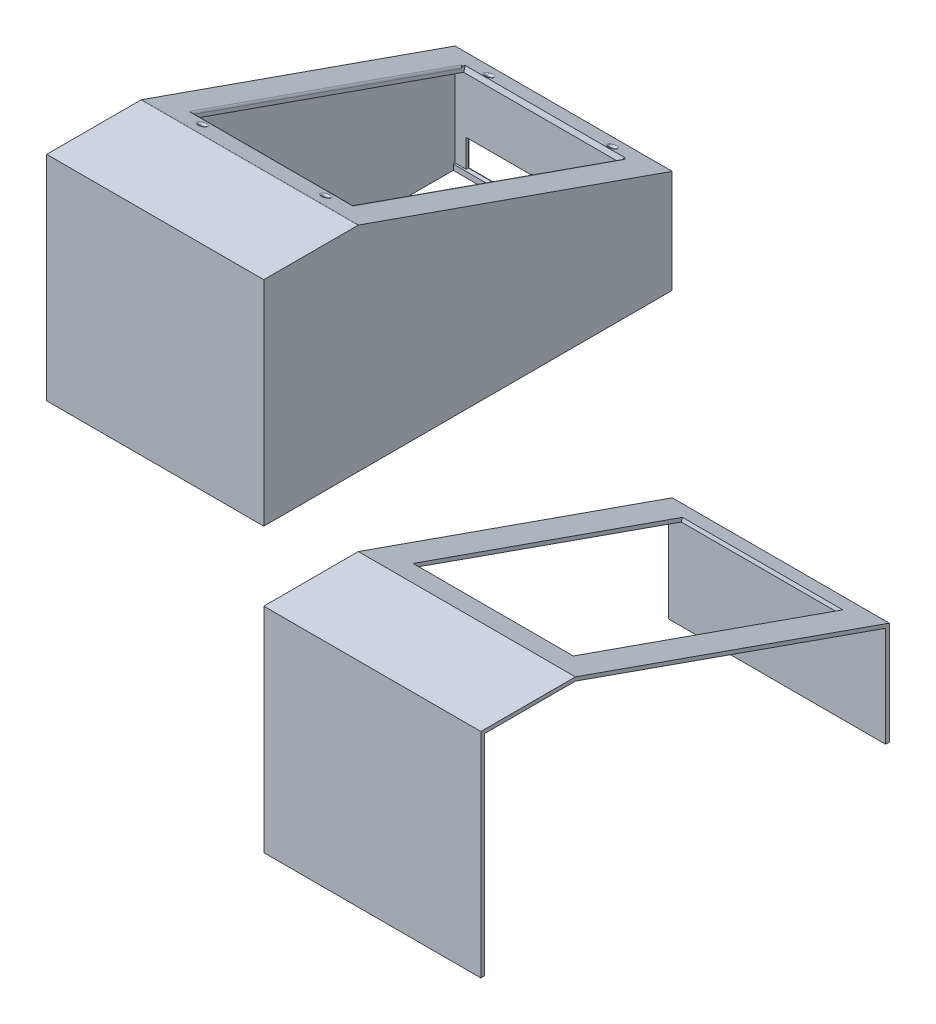
SolidWorks part; units mm, degrees
ref_plane "Alzado" through (0, 0, 0) normal (0, 0, 1) x (1, 0, 0)
ref_plane "Planta" through (0, 0, 0) normal (0, 1, 0) x (1, 0, 0)
ref_plane "Vista lateral" through (0, 0, 0) normal (1, 0, 0) x (0, 0, -1)
sketch "Sketch1" plane through (0, 0, 0) normal (1, 0, 0) x (0, 0, -1)
  line L3 (157.3381, -22.7425) -> (157.3381, 37.2575) construction
  line L4 (157.3381, 37.2575) -> (50.3381, 74.8888)
  line L7 (50.3381, 74.8888) -> (-13.2647, 97.2575)
  line L8 (-13.2647, 97.2575) -> (-64.6619, 97.2575)
  line L9 (-64.6619, 97.2575) -> (-64.6619, 95.2575)
  line L10 (-64.6619, 95.2575) -> (-13.2647, 95.2575)
  line L11 (-13.2647, 95.2575) -> (157.3381, 35.2575)
  line L12 (157.3381, 35.2575) -> (157.3381, -22.7425)
  line L13 (157.3381, -22.7425) -> (159.3381, -22.7425)
  line L14 (157.3381, 37.2575) -> (159.3381, 36.5258)
  line L15 (159.3381, 36.5258) -> (159.3381, -22.7425)
extrude "Boss-Extrude1" add sketch "Sketch1" along normal blind 118
sketch "Sketch2" plane through (0, 0, -159.3381) normal (0, 0, -1) x (-1, 0, 0)
  line L0 (0, -22.7425) -> (-8, -22.7425) construction
  line L1 (-118, -22.7425) -> (0, -22.7425) construction
  line L3 (-8, -22.7425) -> (-52, -22.7425)
  line L4 (-8, -22.7425) -> (-8, -0.7425)
  line L5 (-8, -0.7425) -> (-52, -0.7425)
  line L6 (-52, -22.7425) -> (-52, -0.7425)
  dimension "D1" = 8
  dimension "D2" = 22
  dimension "D3" = 44
extrude "Cut-Extrude1" cut sketch "Sketch2" against normal blind 118
sketch "Sketch3" plane through (0, 95.2575, 0) normal (0, -1, 0) x (1, 0, 0)
  line L0 (118, 64.6619) -> (118, 13.2647) construction
  line L1 (0, 64.6619) -> (118, 64.6619)
  line L2 (0, 64.6619) -> (0, 62.6619)
  line L3 (0, 62.6619) -> (118, 62.6619)
  line L4 (118, 64.6619) -> (118, 62.6619)
  dimension "D1" = 2
sketch "Sketch48" plane through (0, 0, -159.3381) normal (0, 0, -1) x (-1, 0, 0)
  line L0 (-8, -22.7425) -> (-8, -0.7425) construction
  line L1 (-52, -0.7425) -> (-8, -0.7425)
  line L2 (-52, -0.7425) -> (-52, -2.7425)
  line L3 (-52, -2.7425) -> (-8, -2.7425)
  line L4 (-8, -0.7425) -> (-8, -2.7425)
  dimension "D1" = 2
extrude "Boss-Extrude28" add sketch "Sketch48" against normal up to vertex
sketch "Sketch49" plane through (0, 0, -159.3381) normal (0, 0, -1) x (-1, 0, 0)
  line L0 (-8, -22.7425) -> (-8, -2.7425) construction
  line L1 (-52, -2.7425) -> (-8, -2.7425)
  line L2 (-52, -2.7425) -> (-52, -5.2425)
  line L3 (-52, -5.2425) -> (-8, -5.2425)
  line L4 (-8, -2.7425) -> (-8, -5.2425)
  dimension "D1" = 2.5
extrude "Boss-Extrude29" add sketch "Sketch49" against normal up to vertex
sketch "Sketch50" plane through (0, 0, -159.3381) normal (0, 0, -1) x (-1, 0, 0)
  line L0 (-52, -5.2425) -> (-8, -5.2425) construction
  line L1 (-8, -5.2425) -> (-9.5, -5.2425)
  line L2 (-8, -5.2425) -> (-8, -22.7425)
  line L3 (-8, -22.7425) -> (-9.5, -22.7425)
  line L4 (-9.5, -5.2425) -> (-9.5, -22.7425)
  line L5 (-52, -22.7425) -> (-48.5, -22.7425)
  line L6 (-52, -22.7425) -> (-52, -5.2425)
  line L7 (-52, -5.2425) -> (-48.5, -5.2425)
  line L8 (-48.5, -22.7425) -> (-48.5, -5.2425)
  dimension "D1" = 3.5
  dimension "D2" = 1.5
extrude "Boss-Extrude30" add sketch "Sketch50" against normal up to vertex
sketch "Sketch51" plane through (0, 0, -159.3381) normal (0, 0, -1) x (-1, 0, 0)
  line L0 (0, -22.7425) -> (0, 36.5258) construction
  line L1 (-118, -22.7425) -> (0, -22.7425)
  line L2 (-118, -22.7425) -> (-118, -19.2425)
  line L3 (-118, -19.2425) -> (0, -19.2425)
  line L4 (0, -22.7425) -> (0, -19.2425)
  dimension "D1" = 3.5
extrude "Boss-Extrude31" add sketch "Sketch51" against normal up to vertex
sketch "Sketch52" plane through (0, 82.4004, -28.9797) normal (0, 0.9434, -0.3318) x (1, 0, 0)
  line L0 (118, 136.0652) -> (118, -44.7809) construction
  line L1 (15.45, 123.5652) -> (102.55, 123.5652)
  line L2 (15.45, 123.5652) -> (15.45, -31.6348)
  line L3 (15.45, -31.6348) -> (102.55, -31.6348)
  line L4 (102.55, 123.5652) -> (102.55, -31.6348)
  line L6 (118, 136.0652) -> (0, 136.0652) construction
  dimension "D1" = 87.1
  dimension "D2" = 155.2
  dimension "D3" = 15.45
  dimension "D4" = 12.5
extrude "Cut-Extrude11" cut sketch "Sketch52" against normal blind 2
sketch "Sketch53" plane through (0, 0, 0) normal (-1, 0, 0) x (0, 0, 1)
  line L0 (-151.3116, 39.377) -> (-159.3381, 36.5541)
  line L1 (-157.3381, 37.2575) -> (13.2647, 97.2575) construction
  line L2 (-159.3381, 36.5541) -> (-159.3381, 36.3733)
  line L3 (-159.3381, -22.7425) -> (-159.3381, 36.5258) construction
  line L4 (-159.3381, 36.3733) -> (-153.7496, 38.3387)
  line L5 (-153.7496, 38.3387) -> (-151.3116, 39.377)
extrude "Boss-Extrude32" add sketch "Sketch53" against normal up to vertex (118 mm away)
sketch "Sketch54" plane through (0, 80.6205, -28.3538) normal (0, -0.9434, 0.3318) x (1, 0, 0)
  line L0 (15.45, 31.6348) -> (102.55, 31.6348) construction
  line L1 (10.45, -133.5652) -> (107.55, -133.5652)
  line L2 (10.45, -133.5652) -> (10.45, 41.6348)
  line L3 (10.45, 41.6348) -> (107.55, 41.6348)
  line L4 (107.55, -133.5652) -> (107.55, 41.6348)
  line L5 (10.45, -133.5652) -> (107.55, 41.6348) construction
  line L6 (10.45, 41.6348) -> (107.55, -133.5652) construction
  line L7 (15.45, -123.5652) -> (15.45, 31.6348) construction
  line L8 (102.55, 31.6348) -> (102.55, -123.5652) construction
  line L9 (102.55, -123.5652) -> (15.45, -123.5652) construction
  point P0 (59, -45.9652)
  dimension "D1" = 10
  dimension "D2" = 5
  dimension "D3" = 5
  dimension "D4" = 10
extrude "Boss-Extrude33" add sketch "Sketch54" along normal blind 1
sketch "Sketch55" plane through (0, 80.6205, -28.3538) normal (0, 0.9434, -0.3318) x (1, 0, 0)
  line L1 (15.45, 123.5652) -> (102.55, 123.5652)
  line L2 (15.45, 123.5652) -> (15.45, -31.6348)
  line L3 (15.45, -31.6348) -> (102.55, -31.6348)
  line L4 (102.55, 123.5652) -> (102.55, -31.6348)
extrude "Cut-Extrude12" cut sketch "Sketch55" against normal blind 1
sketch "Sketch56" plane through (0, 79.6772, -28.022) normal (0, -0.9434, 0.3318) x (1, 0, 0)
  line L0 (10.45, 41.6348) -> (10.45, -133.5652) construction
  line L1 (15.45, 31.6348) -> (102.55, 31.6348) construction
  line L2 (107.55, -133.5652) -> (107.55, 41.6348) construction
  line L3 (102.55, -123.5652) -> (15.45, -123.5652) construction
  circle A0 centre (92.55, 36.6348) radius 2.5059
  circle A1 centre (25.45, 36.6348) radius 1.5
  circle A2 centre (25.45, -128.5652) radius 1.5
  circle A3 centre (92.55, -128.5652) radius 1.5
  dimension "D1" = 3
  dimension "D7" = 3
  dimension "D9" = 3
  dimension "D2" = 15
  dimension "D3" = 5
  dimension "D4" = 5
  dimension "D5" = 15
  dimension "D6" = 15
  dimension "D8" = 5
  dimension "D10" = 5
  dimension "D11" = 15
extrude "Cut-Extrude13" cut sketch "Sketch56" against normal through all
sketch "Sketch57" plane through (0, 79.6772, -28.022) normal (0, -0.9434, 0.3318) x (1, 0, 0)
  circle A0 centre (92.55, 36.6348) radius 2.5059
extrude "Boss-Extrude35" add sketch "Sketch57" against normal up to vertex (2.8867 mm away)
sketch "Sketch58" plane through (0, 79.6772, -28.022) normal (0, -0.9434, 0.3318) x (1, 0, 0)
  line L0 (15.45, 31.6348) -> (102.55, 31.6348) construction
  line L1 (107.55, -133.5652) -> (107.55, 41.6348) construction
  circle A0 centre (92.55, 36.6348) radius 1.5
  dimension "D1" = 5
  dimension "D2" = 15
extrude "Cut-Extrude14" cut sketch "Sketch58" against normal through all
extrude "Boss-Extrude2" add sketch "Sketch3" along normal blind 114.04
sketch "Sketch5" plane through (0, 0, 64.6619) normal (0, 0, 1) x (1, 0, 0)
  line L7 (118, -18.7825) -> (0, -18.7825) construction
  line L8 (108, -18.7825) -> (69, -18.7825)
  line L9 (108, -18.7825) -> (108, -8.7825)
  line L10 (108, -8.7825) -> (69, -8.7825)
  line L11 (69, -18.7825) -> (69, -8.7825)
  line L12 (59, -18.7825) -> (59, -8.6532) construction
  line L13 (118, 97.2575) -> (118, -18.7825) construction
  dimension "D1" = 10
  dimension "D2" = 10
  dimension "D3" = 10
extrude "Boss-Extrude3" add sketch "Sketch5" against normal blind 10
sketch "Sketch6" plane through (0, 0, 62.6619) normal (0, 0, -1) x (-1, 0, 0)
  line L0 (0, -18.7825) -> (0, 95.2575) construction
  line L1 (-118, -18.7825) -> (0, -18.7825)
  line L2 (-118, -18.7825) -> (-118, -16.7825)
  line L3 (-118, -16.7825) -> (0, -16.7825)
  line L4 (0, -18.7825) -> (0, -16.7825)
  dimension "D1" = 2
extrude "Boss-Extrude4" add sketch "Sketch6" along normal blind 1
sketch "Sketch7" plane through (0, 0, 64.6619) normal (0, 0, 1) x (1, 0, 0)
  line L1 (0, -18.7825) -> (118, -18.7825)
  line L2 (0, -18.7825) -> (0, -22.7425)
  line L3 (0, -22.7425) -> (118, -22.7425)
  line L4 (118, -18.7825) -> (118, -22.7425)
extrude "Cut-Extrude2" cut sketch "Sketch7" against normal through all
sketch "Sketch8" plane through (0, 0, -159.3381) normal (0, 0, -1) x (-1, 0, 0)
  line L0 (0, -18.7825) -> (0, 36.5541) construction
  line L1 (-118, -18.7825) -> (0, -18.7825)
  line L2 (-118, -18.7825) -> (-118, -15.7825)
  line L3 (-118, -15.7825) -> (0, -15.7825)
  line L4 (0, -18.7825) -> (0, -15.7825)
  dimension "D1" = 3
extrude "Boss-Extrude5" add sketch "Sketch8" against normal up to vertex
sketch "Sketch9" plane through (0, 0, 0) normal (-1, 0, 0) x (0, 0, 1)
  line L0 (13.2647, 95.2575) -> (-157.3381, 35.2575) construction
  line L1 (-157.3381, -18.7825) -> (-155.3381, -18.7825)
  line L2 (-157.3381, -18.7825) -> (-157.3381, 35.9609)
  line L3 (-157.3381, 35.9609) -> (-155.3381, 35.9609)
  line L4 (-155.3381, -18.7825) -> (-155.3381, 35.9609)
  dimension "D1" = 2
extrude "Boss-Extrude6" add sketch "Sketch9" against normal up to vertex (118 mm away)
sketch "Sketch12" plane through (0, 0, -157.3381) normal (0, 0, -1) x (-1, 0, 0)
  line L1 (-52, -15.7825) -> (-8, -15.7825)
  line L2 (-52, -15.7825) -> (-52, -0.7425)
  line L3 (-52, -0.7425) -> (-8, -0.7425)
  line L4 (-8, -15.7825) -> (-8, -0.7425)
extrude "Cut-Extrude4" cut sketch "Sketch12" against normal blind 116
sketch "Sketch13" plane through (0, 0, 0) normal (-1, 0, 0) x (0, 0, 1)
  line L1 (-159.3381, -18.7825) -> (-157.3381, -18.7825)
  line L2 (-159.3381, -18.7825) -> (-159.3381, 42.3145)
  line L3 (-159.3381, 42.3145) -> (-157.3381, 42.3145)
  line L4 (-157.3381, -18.7825) -> (-157.3381, 42.3145)
  dimension "D1" = 2
sketch3d "3DSketch1"
  point P0 (82.8961, 95.2575, 47.2846)
sketch "Sketch59" plane through (0, 0, -159.3381) normal (0, 0, -1) x (-1, 0, 0)
  line L1 (-48.5, -5.2425) -> (-43.5, -5.2425)
  line L2 (-48.5, -5.2425) -> (-48.5, -0.2425)
  line L3 (-48.5, -0.2425) -> (-43.5, -0.2425)
  line L4 (-43.5, -5.2425) -> (-43.5, -0.2425)
  dimension "D1" = 5
  dimension "D2" = 5
extrude "Cut-Extrude15" cut sketch "Sketch59" against normal blind 10
extrude "Cut-Extrude5" cut sketch "Sketch13" against normal through all
sketch "Sketch15" plane through (0, 0, -155.3381) normal (0, 0, 1) x (1, 0, 0)
  line L0 (118, -18.7825) -> (118, 35.9609) construction
  line L1 (0, -18.7825) -> (118, -18.7825)
  line L2 (0, -18.7825) -> (0, -15.7825)
  line L3 (0, -15.7825) -> (118, -15.7825)
  line L4 (118, -18.7825) -> (118, -15.7825)
  dimension "D1" = 3
extrude "Boss-Extrude7" add sketch "Sketch15" along normal blind 1
sketch "Sketch26" plane through (118, 0, 0) normal (1, 0, 0) x (0, 0, -1)
  line L0 (-64.6619, -18.7825) -> (-64.6619, 97.2575)
  line L1 (-64.6619, 97.2575) -> (-13.2647, 97.2575)
  line L2 (-13.2647, 97.2575) -> (157.3381, 37.2575)
  line L3 (157.3381, 37.2575) -> (157.3381, -18.7825)
  line L4 (157.3381, -18.7825) -> (-64.6619, -18.7825)
extrude "Boss-Extrude13" add sketch "Sketch26" against normal blind 2
sketch "Sketch28" plane through (0, 0, 0) normal (-1, 0, 0) x (0, 0, 1)
  line L0 (64.6619, -18.7825) -> (64.6619, 97.2575)
  line L1 (64.6619, 97.2575) -> (13.2647, 97.2575)
  line L2 (13.2647, 97.2575) -> (-157.3381, 37.2575)
  line L3 (-157.3381, 37.2575) -> (-157.3381, -18.7825)
  line L4 (-157.3381, -18.7825) -> (64.6619, -18.7825)
extrude "Boss-Extrude16" add sketch "Sketch28" against normal blind 2
fillet "Fillet9" radius 1 31 edges at (30, -15.7825, -157.3381) (59, -18.7825, -157.3381) (50.25, -0.7425, -157.3381) (46, -0.2425, -157.3381) (25.75, -0.7425, -157.3381) (0, 9.2375, -157.3381) (118, 9.2375, -157.3381) (118, -18.7825, -46.3381) (0, 39.2375, 64.6619) (118, 39.2375, 64.6619) (59, -18.7825, 64.6619) (59, 97.2575, 64.6619) (0, 97.2575, 38.9633) (118, 97.2575, 38.9633) (59, 37.2575, -157.3381) (0, 67.2575, -72.0367) (118, 67.2575, -72.0367) (59, 97.2575, 13.2647) (0, -18.7825, -46.3381) (8, -8.2625, -157.3381) (52, -8.2625, -157.3381) (92.55, 94.0572, 4.165) (92.55, 39.2482, -151.6779) (25.45, 39.2482, -151.6779) (25.45, 94.0572, 4.165) (102.55, 67.1503, -72.3414) (59, 41.4047, -145.5461) (15.45, 67.1503, -72.3414) (59, 92.896, 0.8632) (43.5, -0.4925, -157.3381) (48.5, -0.4925, -157.3381)
fillet "Fillet10" radius 1 13 edges at (59, 95.2575, 13.2647) (116, 65.6092, -71.0367) (59, 35.9609, -155.3381) (2, 65.6092, -71.0367) (116, 95.2575, 37.9633) (116, 39.2375, 62.6619) (2, 39.2375, 62.6619) (59, 95.2575, 62.6619) (2, 95.2575, 37.9633) (59, 94.4339, 10.9228) (10.45, 65.3705, -71.7155) (59, 36.3071, -154.3537) (107.55, 65.3705, -71.7155)
sketch "Sketch30" plane through (0, 82.4004, -28.9797) normal (0, 0.9434, -0.3318) x (1, 0, 0)
  line L1 (15.45, 125.5898) -> (102.55, 125.5898)
  line L2 (15.45, 125.5898) -> (15.45, -29.6102)
  line L3 (15.45, -29.6102) -> (102.55, -29.6102)
  line L4 (102.55, 125.5898) -> (102.55, -29.6102)
  line L7 (1, 135.3569) -> (1, -44.6102) construction
  line L9 (1, -44.6102) -> (117, -44.6102) construction
  dimension "D1" = 87.1
  dimension "D2" = 155.2
  dimension "D3" = 14.45
  dimension "D4" = 15
extrude "Cut-Extrude7" cut sketch "Sketch30" against normal through all
sketch "Sketch35" plane through (118, 0, 0) normal (1, 0, 0) x (0, 0, -1)
  line L0 (-13.1037, 97.2009) -> (157.3381, 37.2575)
  line L1 (157.3381, 37.2575) -> (157.3381, -18.7825)
  line L2 (157.3381, -18.7825) -> (-64.6619, -18.7825)
  line L3 (-64.6619, -18.7825) -> (-64.6619, 97.2575)
  line L4 (-64.6619, 97.2575) -> (-13.4355, 97.2575)
  line L5 (-13.1037, 97.2009) -> (-13.2647, 97.2575)
  line L6 (-13.4355, 97.2575) -> (-13.2647, 97.2575)
extrude "Boss-Extrude18" add sketch "Sketch35" against normal blind 2
sketch "Sketch36" plane through (0, 0, 0) normal (-1, 0, 0) x (0, 0, 1)
  line L0 (64.6619, 97.2575) -> (64.6619, -18.7825)
  line L1 (64.6619, -18.7825) -> (-157.3381, -18.7825)
  line L2 (-157.3381, -18.7825) -> (-157.3381, 37.2575)
  line L3 (-157.3381, 37.2575) -> (13.2647, 97.2575)
  line L4 (13.2647, 97.2575) -> (64.6619, 97.2575)
extrude "Boss-Extrude19" add sketch "Sketch36" against normal blind 2
sketch "Sketch37" plane through (0, 0, 0) normal (-1, 0, 0) x (0, 0, 1)
  line L0 (-157.3381, 33.9287) -> (-155.3381, 33.9287)
  line L1 (-157.3381, 37.2575) -> (-157.3381, -18.7825) construction
  line L2 (-155.3381, 33.9287) -> (-155.3381, 37.9609)
  line L3 (13.2647, 97.2575) -> (-157.3381, 37.2575) construction
  line L4 (-155.3381, 37.9609) -> (-157.3381, 37.2575)
  line L5 (-157.3381, 37.2575) -> (-157.3381, 33.9287)
  dimension "D1" = 2
extrude "Boss-Extrude20" add sketch "Sketch37" against normal up to vertex (118 mm away)
sketch "Sketch38" plane through (0, 0, 0) normal (-1, 0, 0) x (0, 0, 1)
  line L0 (64.6619, 97.2575) -> (64.6619, 95.2575)
  line L1 (64.6619, -18.7825) -> (64.6619, 97.2575) construction
  line L2 (64.6619, 97.2575) -> (62.6619, 97.2575)
  line L3 (64.6619, 97.2575) -> (13.2647, 97.2575) construction
  line L4 (64.6619, 95.2575) -> (62.6619, 95.2575)
  line L5 (62.6619, 95.2575) -> (62.6619, 97.2575)
  dimension "D1" = 2
  dimension "D2" = 2
extrude "Boss-Extrude21" add sketch "Sketch38" against normal up to vertex (118 mm away)
sketch "Sketch39" plane through (0, 0, 0) normal (-1, 0, 0) x (0, 0, 1)
  line L1 (64.6619, -18.7825) -> (62.6619, -18.7825)
  line L2 (64.6619, -18.7825) -> (64.6619, -16.7825)
  line L3 (64.6619, -16.7825) -> (62.6619, -16.7825)
  line L4 (62.6619, -18.7825) -> (62.6619, -16.7825)
  dimension "D1" = 2
  dimension "D2" = 2
extrude "Boss-Extrude22" add sketch "Sketch39" against normal up to vertex (118 mm away)
sketch "Sketch40" plane through (0, 0, 0) normal (-1, 0, 0) x (0, 0, 1)
  line L1 (-157.3381, -18.7825) -> (-155.3381, -18.7825)
  line L2 (-157.3381, -18.7825) -> (-157.3381, -16.7825)
  line L3 (-157.3381, -16.7825) -> (-155.3381, -16.7825)
  line L4 (-155.3381, -18.7825) -> (-155.3381, -16.7825)
  dimension "D1" = 2
  dimension "D2" = 2
extrude "Boss-Extrude23" add sketch "Sketch40" against normal up to vertex (118 mm away)
sketch "Sketch41" plane through (0, 97.2575, 0) normal (0, 1, 0) x (1, 0, 0)
  line L1 (118, -64.6619) -> (116, -64.6619)
  line L2 (118, -64.6619) -> (118, -62.6619)
  line L3 (118, -62.6619) -> (116, -62.6619)
  line L4 (116, -64.6619) -> (116, -62.6619)
  line L5 (0, -64.6619) -> (2, -64.6619)
  line L6 (0, -64.6619) -> (0, -62.6619)
  line L7 (0, -62.6619) -> (2, -62.6619)
  line L8 (2, -64.6619) -> (2, -62.6619)
  dimension "D1" = 2
  dimension "D2" = 2
  dimension "D3" = 2
extrude "Boss-Extrude25" add sketch "Sketch41" against normal blind 88
sketch "Sketch42" plane through (118, 0, 0) normal (1, 0, 0) x (0, 0, -1)
  line L0 (-64.6619, -56.4118) -> (-64.6619, -172.4518)
  line L1 (-64.6619, -56.4118) -> (-13.2647, -56.4118)
  line L3 (157.3381, -172.4518) -> (157.3381, -116.4118)
  line L4 (-13.2647, -56.4118) -> (157.3381, -116.4118)
  line L5 (-13.2647, -56.4118) -> (-13.2647, -58.4118) construction
  line L6 (157.3381, -172.4518) -> (155.3381, -172.4518)
  line L7 (155.3381, -172.4518) -> (155.3381, -123.7468)
  line L8 (155.3381, -117.8285) -> (-13.2647, -58.4118)
  line L9 (-13.2647, -58.4118) -> (-62.6619, -58.4118)
  line L10 (155.3381, -123.7468) -> (155.3381, -117.8285)
  line L11 (-62.6619, -58.4118) -> (-62.6619, -172.4518)
  line L12 (-62.6619, -172.4518) -> (-64.6619, -172.4518)
  dimension "D1" = 116.04
  dimension "D2" = 56.04
  dimension "D3" = 2
  dimension "D4" = 2
  dimension "D5" = 2
  dimension "D6" = 2
extrude "Boss-Extrude26" add sketch "Sketch42" along normal blind 118 separate body
sketch "Sketch46" plane through (0, -54.3539, 19.116) normal (0, 0.9434, -0.3318) x (1, 0, 0)
  line L0 (118, 187.0487) -> (118, 6.2025) construction
  line L1 (133.45, 176.5687) -> (220.55, 176.5687)
  line L2 (133.45, 176.5687) -> (133.45, 21.3687)
  line L3 (133.45, 21.3687) -> (220.55, 21.3687)
  line L4 (220.55, 176.5687) -> (220.55, 21.3687)
  line L5 (236, 187.0487) -> (118, 187.0487) construction
  dimension "D1" = 15.45
  dimension "D2" = 87.1
  dimension "D3" = 155.2
  dimension "D4" = 10.48
extrude "Cut-Extrude10" cut sketch "Sketch46" against normal blind 118
sketch "Sketch47" plane through (236, 0, 0) normal (1, 0, 0) x (0, 0, -1)
